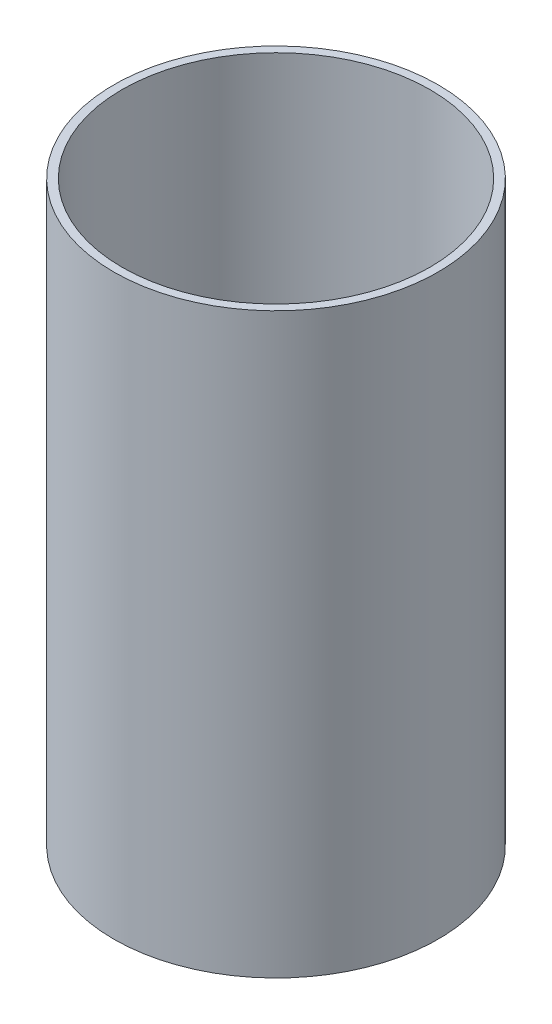
SolidWorks part; units mm, degrees
material "PVC Rigid"
ref_plane "Front Plane" through (0, 0, 0) normal (0, 0, 1) x (1, 0, 0)
ref_plane "Top Plane" through (0, 0, 0) normal (0, 1, 0) x (1, 0, 0)
ref_plane "Right Plane" through (0, 0, 0) normal (1, 0, 0) x (0, 0, -1)
sketch "Sketch1" plane through (0, 0, 0) normal (0, 1, 0) x (1, 0, 0)
  circle A0 centre (0, 0) radius 93.6625
  circle A1 centre (0, 0) radius 88.9
  dimension "D1" = 187.325
  dimension "D2" = 177.8
extrude "Boss-Extrude1" add sketch "Sketch1" along normal mid plane 333.695
